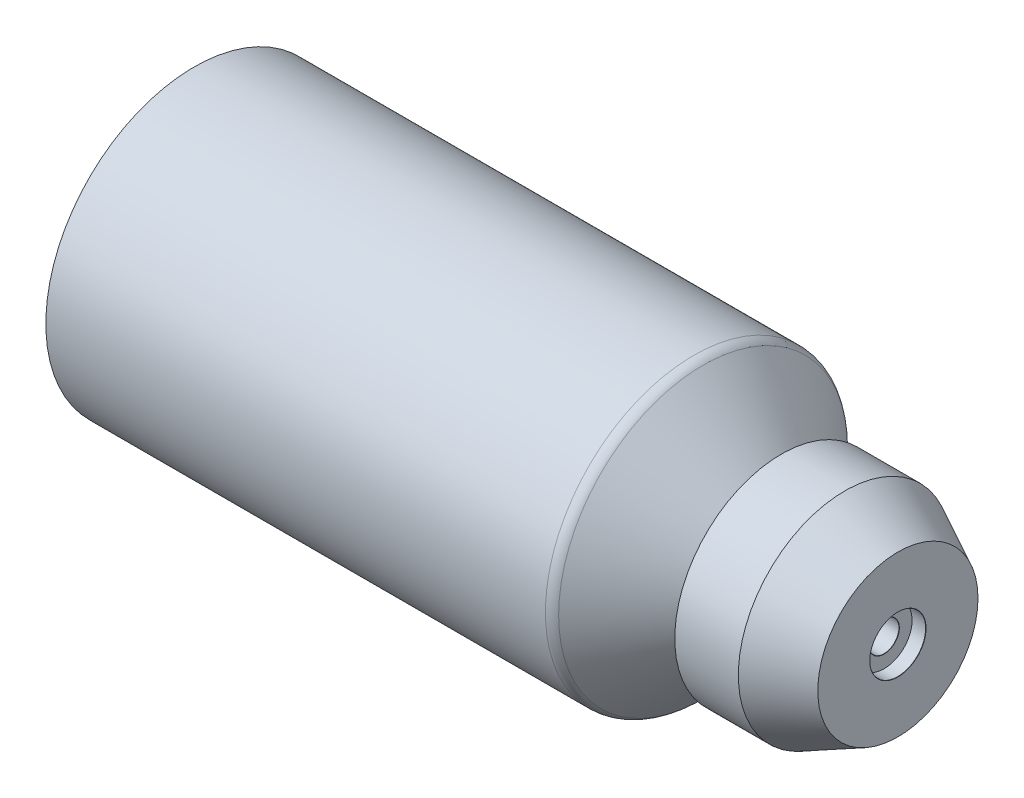
SolidWorks part; units mm, degrees
ref_plane "Front Plane" through (0, 0, 0) normal (0, 0, 1) x (1, 0, 0)
ref_plane "Top Plane" through (0, 0, 0) normal (0, 1, 0) x (1, 0, 0)
ref_plane "Right Plane" through (0, 0, 0) normal (1, 0, 0) x (0, 0, -1)
sketch "Sketch3" plane through (0, 0, 0) normal (0, 0, 1) x (1, 0, 0)
  line L0 (1.7986, 24.13) -> (-76.2, 24.13) construction
  line L1 (-76.2, 17.78) -> (-76.2, 11.43)
  line L2 (-76.2, 24.13) -> (-76.2, 17.78) construction
  line L3 (-76.2, 17.78) -> (-16.3214, 17.78)
  line L4 (-15.1989, 17.315) -> (-5.8214, 7.9375)
  line L5 (-5.8214, 7.9375) -> (-5.8214, -7.9375) construction
  line L6 (-5.8214, 12.7) -> (-5.8214, -12.7) construction
  line L7 (-5.8214, 7.9375) -> (-5.8214, 12.7762)
  line L8 (-5.8214, 12.7762) -> (1.7986, 12.7762)
  line L9 (1.7986, 24.1554) -> (1.7986, -24.1554) construction
  line L10 (1.7986, 12.7762) -> (1.7986, 24.13) construction
  line L11 (24.1721, 0) -> (-63.4646, 0) construction
  line L12 (-76.2, 11.43) -> (-15.6639, 11.43)
  line L13 (-15.6639, 11.43) -> (-15.6639, 0)
  line L14 (-15.6639, 0) -> (-5.8214, 0)
  line L15 (-5.8214, 0) -> (-5.8214, 7.9375) construction
  line L16 (-15.6639, 17.78) -> (-15.6639, 11.43) construction
  line L17 (1.7986, 12.7762) -> (1.7986, 0)
  line L18 (1.7986, 0) -> (-5.8214, 0)
  arc A0 (-16.3214, 17.78) -> (-15.1989, 17.315) centre (-16.3214, 16.1925) cw
  dimension "D7" = 1.5875
  dimension "D1" = 45
  dimension "D2" = 12.7762
  dimension "D3" = 6.35
  dimension "D4" = 24.13
  dimension "D5" = 15.875
  dimension "D6" = 76.2
  dimension "D8" = 6.35
revolve "Revolve1" add sketch "Sketch3" angle 360 about L11
hole_wizard "CBORE for M3 SBHCS1" positions "Sketch4" profile "Sketch6" counterbore size "M3" standard "ANSI Metric" end condition through all
sketch "Sketch4" plane through (-15.6639, 0, 0) normal (-1, 0, 0) x (0, 0, 1)
  point P0 (0, 0)
sketch "Sketch6" plane through (-15.6639, 0, 0) normal (0, 1, 0) x (0, 0, 1)
  line L0 (0, 0) -> (0, 17.4625)
  line L1 (0, 17.4625) -> (1.8, 17.4625)
  line L3 (1.8, 1.675) -> (1.825, 1.65)
  line L4 (1.825, 1.65) -> (3.35, 1.65)
  line L5 (3.35, 1.65) -> (3.35, 0.025)
  line L6 (3.35, 0.025) -> (3.375, 0)
  line L7 (3.375, 0) -> (0, 0)
  line L8 (-3.35, 0.025) -> (-3.375, 0) construction
  line L9 (-1.8, 1.675) -> (-1.825, 1.65) construction
  line L10 (1.8, 17.4625) -> (1.8, 1.675)
  line L11 (0, -6.35) -> (0, 107.95) construction
  dimension "Thru Hole Dia." = 3.6
  dimension "Thru Hole Depth" = 17.4625
  dimension "C'Bore Dia." = 6.7
  dimension "C'Bore Depth" = 1.65
  dimension "Near C'Sink Dia." = 6.75
  dimension "Near C'Sink Angle" = 90
  dimension "Mid C'Sink Dia." = 3.65
  dimension "Mid C'Sink Angle" = 90
ref_plane "split-plane" through (-5.8214, 0, 0) normal (-1, 0, 0) x (0, 0, 1)
sketch "Sketch10" plane through (1.7986, 0, 0) normal (1, 0, 0) x (0, 0, -1)
  circle A2 centre (0, 0) radius 12.7762
  circle A3 centre (0, 0) radius 12.7762
  dimension "D1" = 0
extrude "Boss-Extrude1" add sketch "Sketch10" along normal blind 6.35
chamfer "Chamfer1" distance 6.35 distance2 3.175 1 edges at (8.1486, 0, -12.7762) first distance on face at (-5.8214, 0, -12.7762)
hole_wizard "CBORE for M3 SBHCS3" positions "Sketch11" profile "Sketch12" counterbore size "M3" standard "ANSI Metric" end condition through all
sketch "Sketch11" plane through (8.1486, 0, 0) normal (1, 0, 0) x (0, 0, -1)
  point P0 (0, 0)
sketch "Sketch12" plane through (8.1486, 0, 0) normal (0, 1, 0) x (0, 0, -1)
  line L0 (0, 0) -> (0, 84.3486)
  line L1 (0, 84.3486) -> (1.8, 84.3486)
  line L3 (1.8, 1.675) -> (1.825, 1.65)
  line L4 (1.825, 1.65) -> (3.35, 1.65)
  line L5 (3.35, 1.65) -> (3.35, 0.025)
  line L6 (3.35, 0.025) -> (3.375, 0)
  line L7 (3.375, 0) -> (0, 0)
  line L8 (-3.35, 0.025) -> (-3.375, 0) construction
  line L9 (-1.8, 1.675) -> (-1.825, 1.65) construction
  line L10 (1.8, 84.3486) -> (1.8, 1.675)
  line L11 (0, -6.35) -> (0, 107.95) construction
  dimension "Thru Hole Dia." = 3.6
  dimension "Thru Hole Depth" = 84.3486
  dimension "C'Bore Dia." = 6.7
  dimension "C'Bore Depth" = 1.65
  dimension "Near C'Sink Dia." = 6.75
  dimension "Near C'Sink Angle" = 90
  dimension "Mid C'Sink Dia." = 3.65
  dimension "Mid C'Sink Angle" = 90
split "split" trim tools "split-plane" bodies to split 107 resulting bodies 104 105
